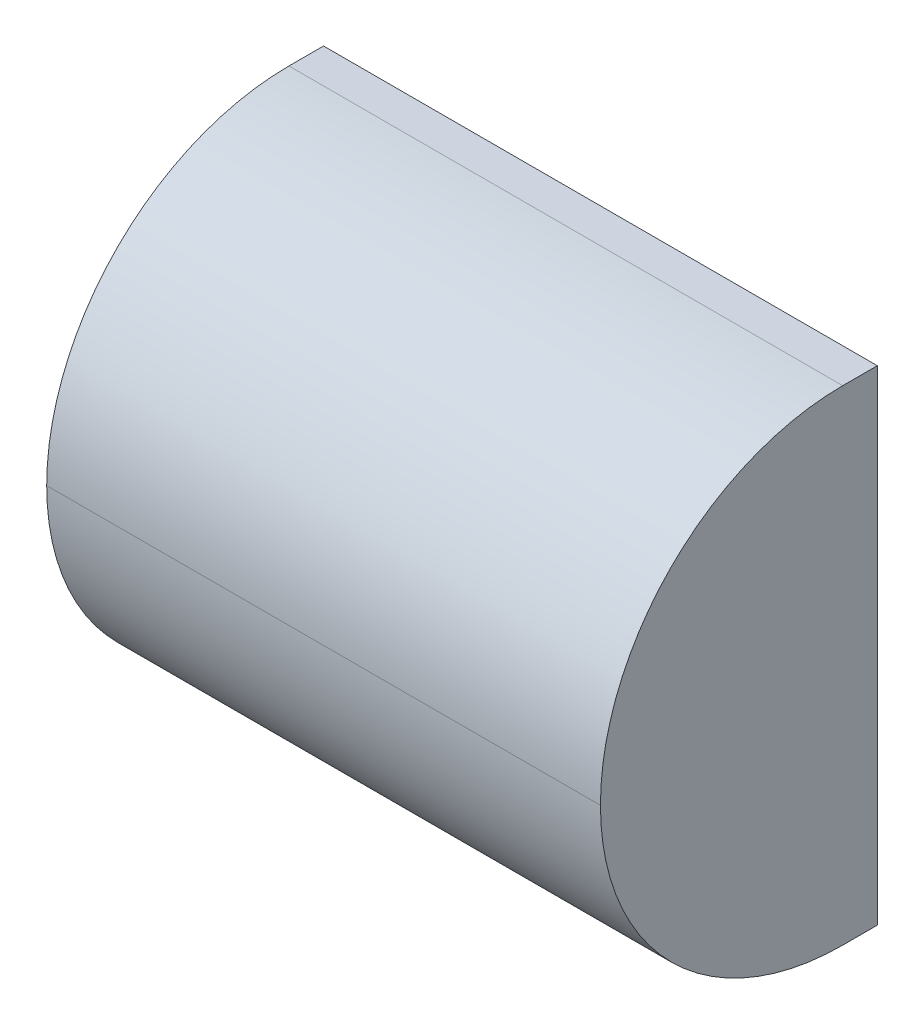
SolidWorks part; units mm, degrees
ref_plane "Front Plane" through (0, 0, 0) normal (0, 0, 1) x (1, 0, 0)
ref_plane "Top Plane" through (0, 0, 0) normal (0, 1, 0) x (1, 0, 0)
ref_plane "Right Plane" through (0, 0, 0) normal (1, 0, 0) x (0, 0, -1)
sketch "Sketch1" plane through (0, 0, 0) normal (0, 0, 1) x (1, 0, 0)
  line L1 (0, 0) -> (8, 0)
  line L2 (0, 0) -> (0, 7)
  line L3 (0, 7) -> (8, 7)
  line L4 (8, 0) -> (8, 7)
  dimension "D1" = 8
  dimension "D2" = 7
extrude "Boss-Extrude1" add sketch "Sketch1" along normal blind 4
fillet "Fillet1" radius 3.5 2 edges at (4, 0, 4) (4, 7, 4)
